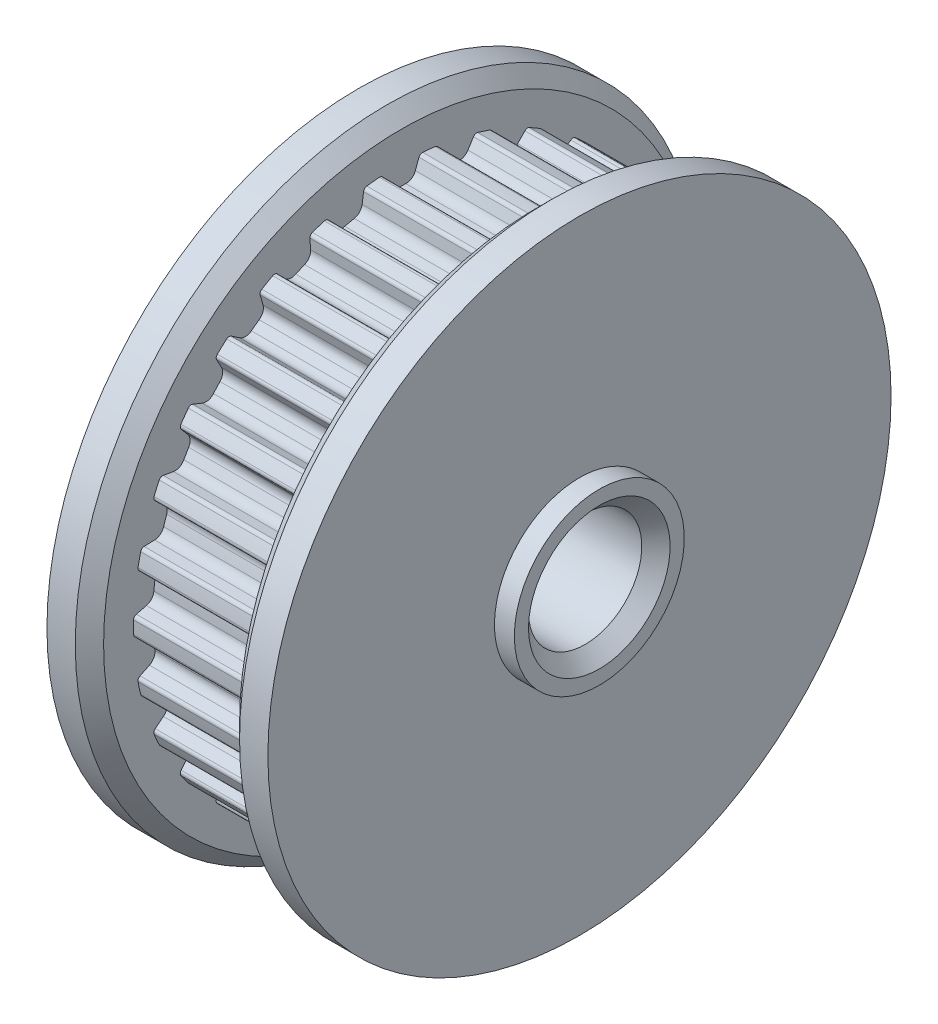
SolidWorks part; units mm, degrees
ref_plane "前视基准面" through (0, 0, 0) normal (0, 0, 1) x (1, 0, 0)
ref_plane "上视基准面" through (0, 0, 0) normal (0, 1, 0) x (1, 0, 0)
ref_plane "右视基准面" through (0, 0, 0) normal (1, 0, 0) x (0, 0, -1)
sketch "草图1" plane through (0, 0, 0) normal (0, 0, 1) x (1, 0, 0)
  line L0 (0, 0) -> (64.8368, 0) construction
  line L1 (0, 2) -> (0, 9.446)
  line L2 (0, 9.446) -> (4.8, 9.446)
  line L3 (4.8, 9.446) -> (4.8, 3)
  line L4 (4.8, 3) -> (7, 3)
  line L5 (7, 3) -> (7, 2)
  line L6 (7, 2) -> (0, 2)
  dimension "L" = 7
  dimension "B" = 4.8
  dimension "d" = 4
  dimension "d1" = 6
  dimension "da" = 18.892
revolve "旋转1" add sketch "草图1" angle 360 about L0
sketch "草图7" plane through (0, 0, 0) normal (-1, 0, 0) x (0, 0, 1)
  circle A0 centre (0, 0) radius 2 construction
  circle A1 centre (0, 0) radius 2
  circle A2 centre (0, 0) radius 11
  dimension "D1" = 22
extrude "凸台-拉伸1" add sketch "草图7" along normal blind 1.5
chamfer "倒角1" distance 0.5 angle 45 2 edges at (7, 0, 2) (-1.5, 0, 2)
ref_axis "基准轴1" through (-0.35, 0, 0) along (1, 0, 0)
sketch "草图6" plane through (0, 0, 0) normal (1, 0, 0) x (0, 0, -1)
  line L0 (0, 0) -> (0, 16.0158) construction
  line L1 (0.6325, 9.3298) -> (0.5069, 8.9846)
  line L2 (0.8947, 9.4035) -> (1.3928, 10.772)
  line L3 (-0.8947, 9.4035) -> (-1.3928, 10.772)
  line L4 (-0.6325, 9.3298) -> (-0.5069, 8.9846)
  arc A1 (0.1711, 8.7543) -> (-0.1711, 8.7543) centre (0, 0) ccw
  arc A2 (0.7652, 9.415) -> (0.8947, 9.4035) centre (0, 0) cw
  arc A3 (0.5069, 8.9846) -> (0.1711, 8.7543) centre (0.178, 9.1043) cw
  arc A4 (0.6325, 9.3298) -> (0.7652, 9.415) centre (0.7547, 9.2854) cw
  arc A5 (1.3928, 10.772) -> (-1.3928, 10.772) centre (0, 0) ccw
  arc A6 (-0.7652, 9.415) -> (-0.8947, 9.4035) centre (0, 0) ccw
  arc A7 (-0.6325, 9.3298) -> (-0.7652, 9.415) centre (-0.7547, 9.2854) ccw
  arc A8 (-0.5069, 8.9846) -> (-0.1711, 8.7543) centre (-0.178, 9.1043) ccw
  circle A9 centre (0, 0) radius 9.446 construction
  point P8 (0, 15.3258)
  point P14 (0.6662, 9.4225)
  point P16 (0.42, 8.7459)
  dimension "D1" = 8.756
  dimension "ra" = 0.13
  dimension "rf" = 0.35
  dimension "D3" = 1.4563
  dimension "D4" = 0.13
  dimension "bw" = 0.84
  dimension "angle" = 40
  dimension "hg" = 0.69
extrude "切除-拉伸2" cut sketch "草图6" along normal up to next
pattern_circular "阵列(圆周)3" count 30 over 360 about axis through (-0.35, 0, 0) along (1, 0, 0) of "切除-拉伸2"
sketch "草图8" plane through (4.8, 0, 0) normal (1, 0, 0) x (0, 0, -1)
  circle A0 centre (0, 0) radius 11 construction
  circle A1 centre (0, 0) radius 3 construction
  circle A2 centre (0, 0) radius 11
  circle A3 centre (0, 0) radius 3
extrude "凸台-拉伸2" add sketch "草图8" along normal blind 1.5 separate body
chamfer "倒角2" distance 0.5 angle 45 1 edges at (0, 0, 11)
chamfer "倒角3" distance 0.5 angle 45 2 edges at (4.8, 0, -11) (4.8, 0, -3)
equation "\"D4@草图6\" = \"ra@草图6\""
equation "\"D1@草图6\" = \"da@草图1\" / 2 - \"hg@草图6\" "
